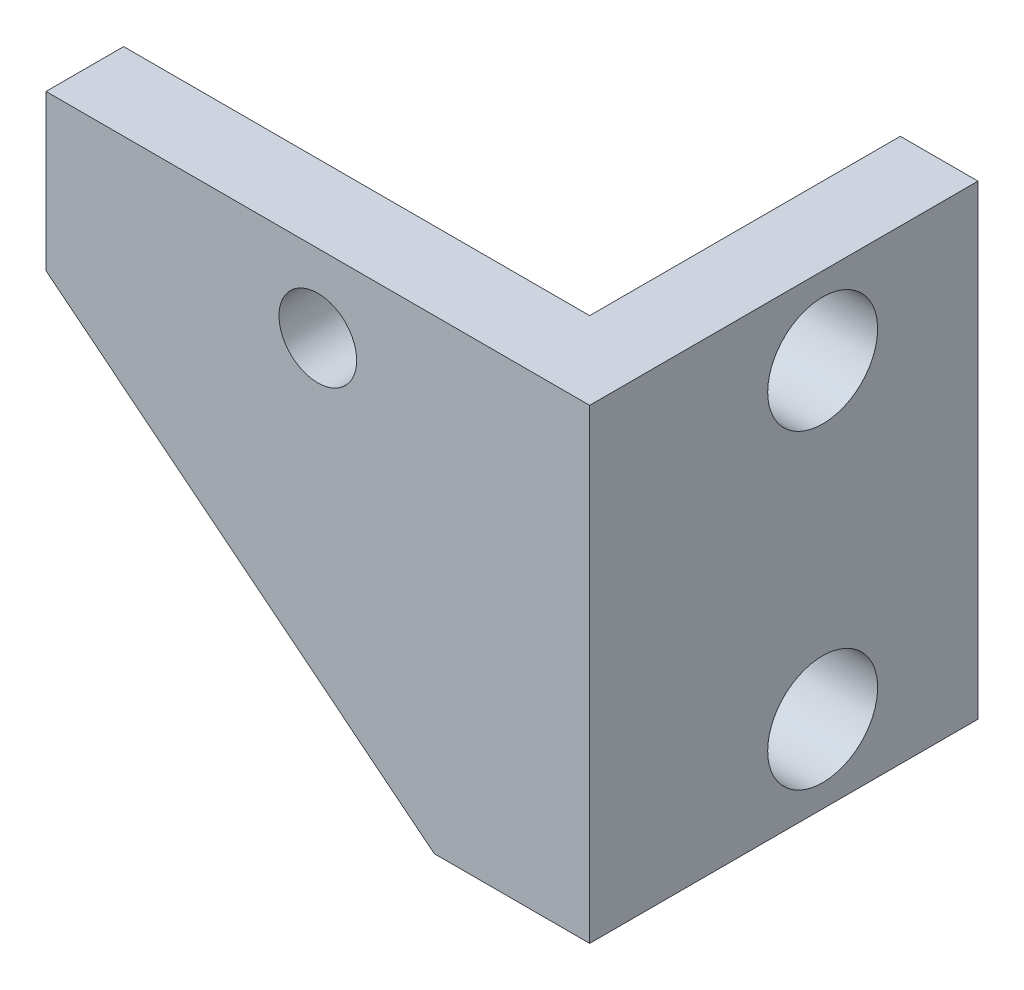
SolidWorks part; units mm, degrees
ref_plane "Front Plane" through (0, 0, 0) normal (0, 0, 1) x (1, 0, 0)
ref_plane "Top Plane" through (0, 0, 0) normal (0, 1, 0) x (1, 0, 0)
ref_plane "Right Plane" through (0, 0, 0) normal (1, 0, 0) x (0, 0, -1)
sketch "Sketch1" plane through (0, 0, 0) normal (0, 0, 1) x (1, 0, 0)
  line L0 (0, 0) -> (-22.225, 0)
  line L1 (-22.225, 0) -> (-22.225, -6.35)
  line L2 (-22.225, -6.35) -> (-6.35, -19.05)
  line L3 (-6.35, -19.05) -> (0, -19.05)
  line L4 (0, -19.05) -> (0, 0)
  dimension "D1" = 6.35
  dimension "D2" = 19.05
  dimension "D3" = 22.225
extrude "Boss-Extrude1" add sketch "Sketch1" along normal blind 3.175
hole_wizard "1/8 (0.1250) Dowel Hole2" positions "Sketch5" profile "Sketch6" hole size "1/8" standard "ANSI Inch" end condition through all
sketch "Sketch5" plane through (0, 0, 3.175) normal (0, 0, 1) x (1, 0, 0)
  line L0 (-22.225, -3.175) -> (0, -3.175) construction
  line L1 (-22.225, 0) -> (-22.225, -6.35) construction
  line L2 (0, -19.05) -> (0, 0) construction
  point P10 (-11.1125, -3.175)
sketch "Sketch6" plane through (-11.1125, -3.175, 3.175) normal (1, 0, 0) x (0, -1, 0)
  line L0 (0, 0) -> (0, 3.175)
  line L1 (0, 3.175) -> (1.5875, 3.175)
  line L2 (1.5875, 3.175) -> (1.5875, 0)
  line L5 (1.5875, 0) -> (0, 0)
  line L11 (0, -6.35) -> (0, 107.95) construction
  dimension "Thru Hole Dia." = 3.175
  dimension "Thru Hole Depth" = 3.175
sketch "Sketch7" plane through (0, 0, 3.175) normal (0, 0, 1) x (1, 0, 0)
  line L0 (-6.35, -19.05) -> (0, -19.05) construction
  line L1 (0, 0) -> (-3.175, 0)
  line L2 (0, 0) -> (0, -19.05)
  line L3 (0, -19.05) -> (-3.175, -19.05)
  line L4 (-3.175, 0) -> (-3.175, -19.05)
extrude "Boss-Extrude2" add sketch "Sketch7" against normal blind 15.875
hole_wizard "#8 Clearance Hole1" positions "Sketch8" profile "Sketch9" hole size "#8" standard "ANSI Inch" end condition through all
sketch "Sketch8" plane through (-3.175, 0, 0) normal (-1, 0, 0) x (0, 0, 1)
  line L0 (-6.35, 0) -> (-6.35, -3.175) construction
  line L1 (-12.7, 0) -> (0, 0) construction
  line L2 (-6.35, -3.175) -> (-6.35, -15.875) construction
  line L3 (-6.35, -15.875) -> (-6.35, -19.05) construction
  line L4 (-12.7, -19.05) -> (0, -19.05) construction
  point P2 (-6.35, -3.175)
  point P6 (-6.35, -15.875)
  dimension "D1" = 3.175
sketch "Sketch9" plane through (-3.175, -15.875, -6.35) normal (0, 1, 0) x (0, 0, 1)
  line L0 (0, 0) -> (0, 3.175)
  line L1 (0, 3.175) -> (2.2479, 3.175)
  line L2 (2.2479, 3.175) -> (2.2479, 0)
  line L5 (2.2479, 0) -> (0, 0)
  line L11 (0, -6.35) -> (0, 107.95) construction
  dimension "Thru Hole Dia." = 4.4958
  dimension "Thru Hole Depth" = 3.175
